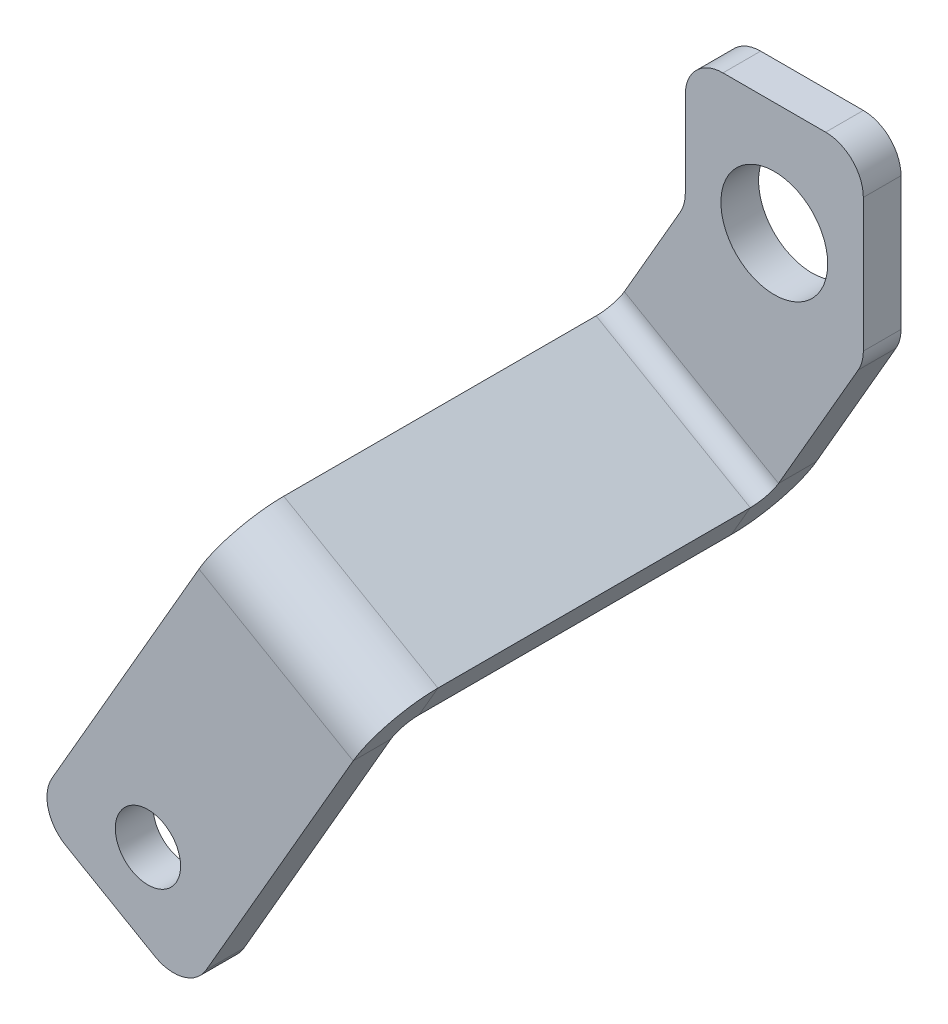
SolidWorks part; units mm, degrees
note: The reader was unsure of these and kept them because the rebuilt part matched: thickness of "Base-Flange1", "Edge-Flange1", "Edge-Flange2"; flange length of "Edge-Flange1", "Edge-Flange2".
material "3003-H14"
ref_plane "X-Y Datum" through (0, 0, 0) normal (0, 0, 1) x (1, 0, 0)
ref_plane "X-Z Datum" through (0, 0, 0) normal (0, 1, 0) x (1, 0, 0)
ref_plane "Y-Z Datum" through (0, 0, 0) normal (1, 0, 0) x (0, 0, -1)
sketch "Sketch2" plane through (0, 0, 0) normal (0, 0, 1) x (1, 0, 0)
  line L0 (-136.8621, 27.1278) -> (-149.8525, 34.6278) construction
  line L4 (-136.8621, 27.1278) -> (-140.0371, 21.6286)
  line L5 (-140.0371, 21.6286) -> (-153.0275, 29.1286)
  line L6 (-153.0275, 29.1286) -> (-149.8525, 34.6278)
  line L7 (-136.8621, 27.1278) -> (-126.0671, 45.8253)
  line L8 (-154.0481, 28.0608) -> (-140.4515, 20.2108) construction
  line L9 (-154.0481, 28.0608) -> (-140.4515, 20.2108) construction
  line L10 (-126.0671, 45.8253) -> (-139.0575, 53.3253)
  line L11 (-139.0575, 53.3253) -> (-149.8525, 34.6278)
  circle A0 centre (-143.3573, 30.8778) radius 2.5 construction
  circle A1 centre (-143.3573, 30.8778) radius 2.5 construction
  circle A2 centre (-143.3573, 30.8778) radius 5.08 construction
  point P6 (-143.3573, 30.8778)
  dimension "D2" = 10.16
  dimension "D1" = 15
  dimension "D3" = 6.35
  dimension "D4" = 21.59
base flange "Base-Flange1" sketch "Sketch2" thickness 3.175 reverse thickness direction yes parameters "D1"=10
edge flange "Edge-Flange1" sketch "Sketch11" flange angle 90 flange length 31.075 flange position bend outside bend radius 1.5875 thickness 3.175 relief rectangular parameters "D6"=0
sketch "Sketch11" plane through (-11.6738, -20.2197, 0) normal (0.5, 0.866, 0) x (0.866, -0.5, 0)
  line L0 (-132.0899, 0) -> (-147.0899, 0) construction
  line L1 (-132.0899, 0) -> (-147.0899, 0)
  line L2 (-147.0899, 0) -> (-147.0899, 27.9)
  line L3 (-147.0899, 27.9) -> (-132.0899, 27.9)
  line L4 (-132.0899, 27.9) -> (-132.0899, 0)
bend "EdgeBend1" bend radius 1.5875 bend angle 90 parameters "D5"=1
edge flange "Edge-Flange2" sketch "Sketch14" flange angle 90 flange length 9.525 flange position bend outside bend radius 1.5875 thickness 3.175 relief rectangular parameters "D6"=0
sketch "Sketch14" plane through (-9.2926, -16.0952, -27.9) normal (0, 0, -1) x (-0.866, 0.5, 0)
  line L2 (132.0899, 0) -> (132.0899, 6.35)
  line L3 (132.0899, 6.35) -> (147.0899, 6.35)
  line L4 (147.0899, 6.35) -> (147.0899, 0)
  line L7 (132.0899, 0) -> (147.0899, 0) construction
  line L8 (132.0899, 0) -> (147.0899, 0)
bend "EdgeBend2" bend radius 1.5875 bend angle 90 parameters "D5"=2
sketch "Sketch15" plane through (0, 0, -32.6625) normal (0, 0, -1) x (-1, 0, 0)
  line L0 (133.5012, 62.949) -> (120.5108, 55.449) construction
  line L1 (133.5012, 62.949) -> (120.5108, 55.449)
  line L2 (130.7483, 78.9379) -> (115.7483, 78.9379)
  line L3 (120.5108, 55.449) -> (115.7483, 63.6979)
  line L4 (115.7483, 63.6979) -> (115.7483, 78.9379)
  line L5 (130.7483, 78.9379) -> (130.7483, 67.7171)
  line L6 (130.7483, 67.7171) -> (133.5012, 62.949)
  point P2 (114.4988, 78.259)
  point P5 (123.2483, 78.9379)
  dimension "D1" = 15
  dimension "D2" = 15.24
  dimension "D3" = 9.525
extrude "Boss-Extrude1" add sketch "Sketch15" against normal blind 3.175
hole_wizard "M5 Clearance Hole1" positions "Sketch16" profile "Sketch17" hole size "M5" standard "ANSI Metric" end condition through all
sketch "Sketch16" plane through (0, 0, 3.175) normal (0, 0, 1) x (1, 0, 0)
  point P0 (-143.3573, 30.8778)
sketch "Sketch17" plane through (-143.3573, 30.8778, 3.175) normal (1, 0, 0) x (0, -1, 0)
  line L0 (0, 0) -> (0, 35.8375)
  line L1 (0, 35.8375) -> (2.75, 35.8375)
  line L2 (2.75, 35.8375) -> (2.75, 0)
  line L5 (2.75, 0) -> (0, 0)
  line L11 (0, -6.35) -> (0, 107.95) construction
  dimension "Thru Hole Dia." = 5.5
  dimension "Thru Hole Depth" = 35.8375
fillet "Fillet1" radius 3.175 6 edges at (-115.7483, 63.6979, -31.075) (-130.7483, 67.7171, -31.075) (-130.7483, 78.9379, -31.075) (-115.7483, 78.9379, -31.075) (-140.0371, 21.6286, 1.5875) (-153.0275, 29.1286, 1.5875)
sketch "Sketch20" plane through (0, 0, -29.4875) normal (0, 0, 1) x (1, 0, 0)
  line L0 (-118.8795, 69.8066) -> (-118.8795, 69.0154) construction
  line L1 (-127.6171, 69.0154) -> (-127.6171, 69.8066) construction
  line L2 (-118.8795, 69.8066) -> (-118.8795, 69.0154) construction
  line L3 (-127.6171, 69.0154) -> (-127.6171, 69.8066) construction
  line L4 (-127.6171, 69.411) -> (-118.8795, 69.411) construction
  arc A0 (-127.6171, 69.0154) -> (-118.8795, 69.0154) centre (-123.2483, 69.0154) ccw construction
  arc A1 (-118.8795, 69.8066) -> (-127.6171, 69.8066) centre (-123.2483, 69.8066) ccw construction
  arc A2 (-127.6171, 69.0154) -> (-118.8795, 69.0154) centre (-123.2483, 69.0154) ccw construction
  arc A3 (-118.8795, 69.8066) -> (-127.6171, 69.8066) centre (-123.2483, 69.8066) ccw construction
  point P8 (-123.2483, 69.411)
hole_wizard "M8 Clearance Hole1" positions "Sketch23" profile "Sketch24" hole size "M8" standard "ANSI Metric" end condition through all
sketch "Sketch23" plane through (0, 0, -29.4875) normal (0, 0, 1) x (1, 0, 0)
  point P0 (-123.2483, 69.411)
sketch "Sketch24" plane through (-123.2483, 69.411, -29.4875) normal (1, 0, 0) x (0, -1, 0)
  line L0 (0, 0) -> (0, 3.175)
  line L1 (0, 3.175) -> (4.5, 3.175)
  line L2 (4.5, 3.175) -> (4.5, 0)
  line L5 (4.5, 0) -> (0, 0)
  line L11 (0, -6.35) -> (0, 107.95) construction
  dimension "Thru Hole Dia." = 9
  dimension "Thru Hole Depth" = 3.175
sketch "Bend-Lines1" [suppressed] plane through (0, 0, 0) normal (0, 1, 0) x (1, 0, 0)
sketch "Bounding-Box1" [suppressed] plane through (0, 0, 0) normal (0, 1, 0) x (1, 0, 0)
sheet metal parameters "Sheet-Metal1" thickness 3.175 parameters "D1"=10
flat pattern "Flat-Pattern1" [suppressed]
sketch "Bend-Lines2" plane through (0, 0, 0) normal (0, 1, 0) x (1, 0, 0)
sketch3d "Bounding-Box2" [suppressed]
  line L0 (139.8145, 21.6286, 0) -> (127.1145, 43.6256, 0) construction
  line L1 (152.8049, 29.1286, 0) -> (140.1049, 51.1256, 0) construction
  line L2 (139.8145, 21.6286, 0) -> (152.8049, 29.1286, 0) construction
  line L3 (127.1145, 43.6256, 0) -> (140.1049, 51.1256, 0) construction
sheet metal parameters "Sheet-Metal2" thickness 3.175 parameters "D1"=10
flat pattern "Flat-Pattern1"
sketch "Bend-Lines2" plane through (0, 0, 0) normal (0, 0, -1) x (-1, 0, 0)
  line L0 (138.858, 53.2852) -> (125.8677, 45.7852) construction
  line L1 (138.858, 53.2852) -> (125.8677, 45.7852) construction
sketch3d "Bounding-Box2" [suppressed]
  line L0 (139.8145, 21.6286, 0) -> (107.9521, 76.8158, 0) construction
  line L1 (152.8049, 29.1286, 0) -> (120.9425, 84.3158, 0) construction
  line L2 (139.8145, 21.6286, 0) -> (152.8049, 29.1286, 0) construction
  line L3 (107.9521, 76.8158, 0) -> (120.9425, 84.3158, 0) construction
bend of the flat pattern "Flatten-<EdgeBend1>1"
sheet metal parameters "Sheet-Metal3" thickness 3.175 parameters "D1"=10
flat pattern "Flat-Pattern1"
sketch "Bend-Lines2" plane through (0, 0, 0) normal (0, 0, -1) x (-1, 0, 0)
  line L0 (138.858, 53.2852) -> (125.8677, 45.7852) construction
  line L1 (138.858, 53.2852) -> (125.8677, 45.7852) construction
  line L2 (120.0332, 85.8908) -> (107.0428, 78.3908) construction
  line L3 (120.0332, 85.8908) -> (107.0428, 78.3908) construction
sketch3d "Bounding-Box2" [suppressed]
  line L0 (139.8145, 21.6286, 0) -> (101.8272, 87.4245, 0) construction
  line L1 (152.8049, 29.1286, 0) -> (114.8176, 94.9245, 0) construction
  line L2 (139.8145, 21.6286, 0) -> (152.8049, 29.1286, 0) construction
  line L3 (101.8272, 87.4245, 0) -> (114.8176, 94.9245, 0) construction
bend of the flat pattern "Flatten-<EdgeBend1>1"
bend of the flat pattern "Flatten-<EdgeBend2>1"
sheet metal parameters "Sheet-Metal4" thickness 3.175 parameters "D1"=10
flat pattern "Flat-Pattern1"
sketch "Bend-Lines2" plane through (0, 0, 0) normal (0, 0, -1) x (-1, 0, 0)
  line L0 (137.4931, 56.0348) -> (124.5028, 48.5348) construction
  line L1 (137.4931, 56.0348) -> (124.5028, 48.5348) construction
  line L2 (118.6682, 88.6405) -> (105.6779, 81.1405) construction
  line L3 (118.6682, 88.6405) -> (105.6779, 81.1405) construction
sketch3d "Bounding-Box2" [suppressed]
  line L0 (135.3379, 19.2877, 0) -> (91.205, 107.8835, 0) construction
  line L1 (153.4381, 28.3041, 0) -> (109.3052, 116.8999, 0) construction
  line L2 (135.3379, 19.2877, 0) -> (153.4381, 28.3041, 0) construction
  line L3 (91.205, 107.8835, 0) -> (109.3052, 116.8999, 0) construction
bend of the flat pattern "Flatten-<EdgeBend1>1"
bend of the flat pattern "Flatten-<EdgeBend2>1"
sheet metal parameters "Sheet-Metal5" thickness 3.175 parameters "D1"=10
flat pattern "Flat-Pattern1"
sketch "Bend-Lines2" plane through (0, 0, 0) normal (0, 0, -1) x (-1, 0, 0)
  line L0 (137.8106, 55.4849) -> (124.8203, 47.9849) construction
  line L1 (137.8106, 55.4849) -> (124.8203, 47.9849) construction
  line L2 (122.1607, 82.5913) -> (109.1704, 75.0913) construction
  line L3 (122.1607, 82.5913) -> (109.1704, 75.0913) construction
sketch3d "Bounding-Box2" [suppressed]
  line L0 (135.7169, 19.5805, 0) -> (94.9581, 101.3571, 0) construction
  line L1 (153.3106, 28.3495, 0) -> (112.5518, 110.1261, 0) construction
  line L2 (135.7169, 19.5805, 0) -> (153.3106, 28.3495, 0) construction
  line L3 (94.9581, 101.3571, 0) -> (112.5518, 110.1261, 0) construction
bend of the flat pattern "Flatten-<EdgeBend1>1"
bend of the flat pattern "Flatten-<EdgeBend2>1"
sheet metal parameters "Sheet-Metal6" thickness 3.175 parameters "D1"=10
flat pattern "Flat-Pattern1" [suppressed]
sketch "Bend-Lines2" plane through (0, 0, 0) normal (0, 0, -1) x (-1, 0, 0)
  line L0 (137.8106, 55.4849) -> (124.8203, 47.9849) construction
  line L1 (137.8106, 55.4849) -> (124.8203, 47.9849) construction
  line L2 (122.1607, 82.5913) -> (109.1704, 75.0913) construction
  line L3 (122.1607, 82.5913) -> (109.1704, 75.0913) construction
sketch3d "Bounding-Box2" [suppressed]
  line L0 (136.1013, 19.8317, 0) -> (95.1744, 100.8089, 0) construction
  line L1 (153.1731, 28.46, 0) -> (112.2463, 109.4372, 0) construction
  line L2 (136.1013, 19.8317, 0) -> (153.1731, 28.46, 0) construction
  line L3 (95.1744, 100.8089, 0) -> (112.2463, 109.4372, 0) construction
bend of the flat pattern "Flatten-<EdgeBend1>1"
bend of the flat pattern "Flatten-<EdgeBend2>1"
sketch "Sketch20-1" [suppressed] plane through (14.9685, 25.9262, 3.175) normal (0, 0, 1) x (1, 0, 0)
  line L2 (-118.8795, 69.8066) -> (-118.8795, 69.0154) construction
  line L3 (-127.6171, 69.0154) -> (-127.6171, 69.8066) construction
  line L4 (-127.6171, 69.411) -> (-118.8795, 69.411) construction
  arc A2 (-127.6171, 69.0154) -> (-118.8795, 69.0154) centre (-123.2483, 69.0154) ccw construction
  arc A3 (-118.8795, 69.8066) -> (-127.6171, 69.8066) centre (-123.2483, 69.8066) ccw construction
  point P8 (-123.2483, 69.411)
